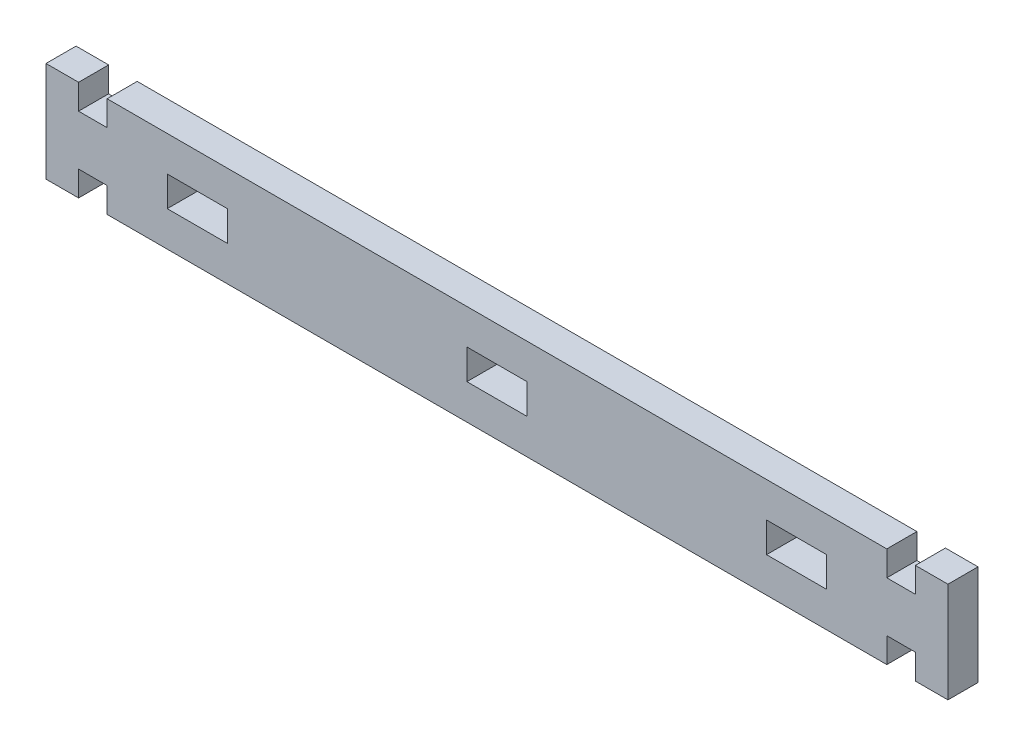
SolidWorks part; units mm, degrees
ref_plane "Front Plane" through (0, 0, 0) normal (0, 0, 1) x (1, 0, 0)
ref_plane "Top Plane" through (0, 0, 0) normal (0, 1, 0) x (1, 0, 0)
ref_plane "Right Plane" through (0, 0, 0) normal (1, 0, 0) x (0, 0, -1)
sketch "Sketch2" plane through (0, 0, 0) normal (0, 1, 0) x (1, 0, 0)
  line L0 (0, 0) -> (0, 6) construction
  dimension "D1" = 6
sketch "Sketch1" plane through (0, 0, 0) normal (0, 0, 1) x (1, 0, 0)
  line L0 (0, 0) -> (0, -10) construction
  line L1 (-90, -10) -> (90, -10)
  line L2 (-90, -10) -> (-90, 10)
  line L3 (-90, 10) -> (90, 10)
  line L4 (90, -10) -> (90, 10)
  line L5 (-90, -10) -> (90, 10) construction
  line L6 (-90, 10) -> (90, -10) construction
  line L7 (-90, 10) -> (-83.5, 10)
  line L8 (-90, 10) -> (-90, -10)
  line L9 (-90, -10) -> (-83.5, -10)
  line L10 (-83.5, 10) -> (-83.5, -10)
  line L11 (-83.5, -10) -> (-77.8, -10)
  line L12 (-83.5, -10) -> (-83.5, -5)
  line L13 (-83.5, -5) -> (-77.8, -5)
  line L14 (-77.8, -10) -> (-77.8, -5)
  line L15 (-83.5, 10) -> (-77.8, 10)
  line L16 (-83.5, 10) -> (-83.5, 5)
  line L17 (-83.5, 5) -> (-77.8, 5)
  line L18 (-77.8, 10) -> (-77.8, 5)
  line L19 (83.5, -5) -> (77.8, -5)
  line L20 (77.8, -10) -> (77.8, -5)
  line L21 (83.5, -10) -> (77.8, -10)
  line L22 (83.5, -10) -> (83.5, -5)
  line L23 (90, -10) -> (83.5, -10)
  line L24 (83.5, 10) -> (83.5, -10)
  line L25 (90, 10) -> (83.5, 10)
  line L26 (90, 10) -> (90, -10)
  line L27 (83.5, 5) -> (77.8, 5)
  line L28 (77.8, 10) -> (77.8, 5)
  line L29 (83.5, 10) -> (77.8, 10)
  line L30 (83.5, 10) -> (83.5, 5)
  line L31 (59.8, 0) -> (0, 0) construction
  line L32 (6, -3) -> (-6, -3)
  line L33 (6, -3) -> (6, 3)
  line L34 (6, 3) -> (-6, 3)
  line L35 (-6, -3) -> (-6, 3)
  line L36 (6, -3) -> (-6, 3) construction
  line L37 (6, 3) -> (-6, -3) construction
  line L38 (-65.8, -3) -> (-53.8, -3)
  line L39 (-65.8, -3) -> (-65.8, 3)
  line L40 (-65.8, 3) -> (-53.8, 3)
  line L41 (-53.8, -3) -> (-53.8, 3)
  line L42 (-65.8, -3) -> (-53.8, 3) construction
  line L43 (-65.8, 3) -> (-53.8, -3) construction
  line L44 (53.8, -3) -> (65.8, -3)
  line L45 (53.8, -3) -> (53.8, 3)
  line L46 (53.8, 3) -> (65.8, 3)
  line L47 (65.8, -3) -> (65.8, 3)
  line L48 (53.8, -3) -> (65.8, 3) construction
  line L49 (53.8, 3) -> (65.8, -3) construction
  line L50 (0, 0) -> (-59.8, 0) construction
  line L51 (65.8, 0) -> (77.8, 0) construction
  line L52 (77.8, 0) -> (77.8, -5) construction
  point P0 (0, 0)
  point P28 (-59.8, 0)
  point P33 (59.8, 0)
  dimension "D1" = 20
  dimension "D2" = 180
  dimension "D3" = 6.5
  dimension "D4" = 5.7
  dimension "D5" = 10
  dimension "D6" = 12
  dimension "D7" = 6
  dimension "D8" = 12
extrude "Boss-Extrude1" add sketch "Sketch1" against normal up to vertex (6 mm away) contours L10 L3 L2 L1 | L28 L3 L18 L17 L10 L13 L14 L1 L20 L19 L24 L27 | L3 L24 L22 L1 L4 region at (-86.75, 0, 0) region at (-76.1181, -7.5, 0) region at (86.75, 0, 0) up to point (0, 0, -6)
equation "\"t_wood\"= 6' Thickness of the wood"
equation "\"t_glass\"= 2.5'Thickness of glass panels"
equation "\"w_glass\"= 181"
equation "\"h_glass\"= 151"
equation "\"h_food_internal\" = 60"
equation "\"entry_height\"= 20"
equation "\"entry diameter\"= 8"
equation "\"glass_bottom_overlap\"= 8"
equation "\"default_finger_size\"= 12"
equation "\"brood_depth\"= 42"
equation "\"outer_box_depth\" = \"brood_depth\" + ( 2 * \"t_glass\" ) + ( 2 * \"t_wood\" )"
equation "\"outer_box_width\"= \"w_glass\" + ( 2 * \"t_wood\" )"
equation "\"food_top_clearance\"= 10"
equation "\"outer_box_height\"= \"t_wood\" + \"h_glass\" + \"t_wood\" + \"h_food_internal\" + \"food_top_clearance\" + \"t_wood\""
equation "\"food_internal_depth\"= \"brood_depth\" + \"t_glass\" + \"t_glass\" - \"t_wood\" - \"t_wood\""
equation "\"food_channel_clearance_width\"= 14"
equation "\"bar_top_play\"= 0.5"
equation "\"bar_entry_angle\"= 10"
equation "\"bar_width\"= 20"
equation "\"entry_disk_play\"= 0.3"
equation "\"D1@Sketch2\"=\"t_wood\""
equation "\"D2@Sketch1\"=\"w_glass\"-1"
equation "\"D3@Sketch1\"=\"t_wood\"+0.5"
equation "\"D4@Sketch1\"=\"t_wood\"-0.3"
equation "\"D6@Sketch1\"=\"default_finger_size\""
equation "\"D7@Sketch1\"=\"t_wood\""
equation "\"D8@Sketch1\"=\"t_wood\"*2"
equation "\"D5@Sketch1\"=\"bar_width\"/2"
